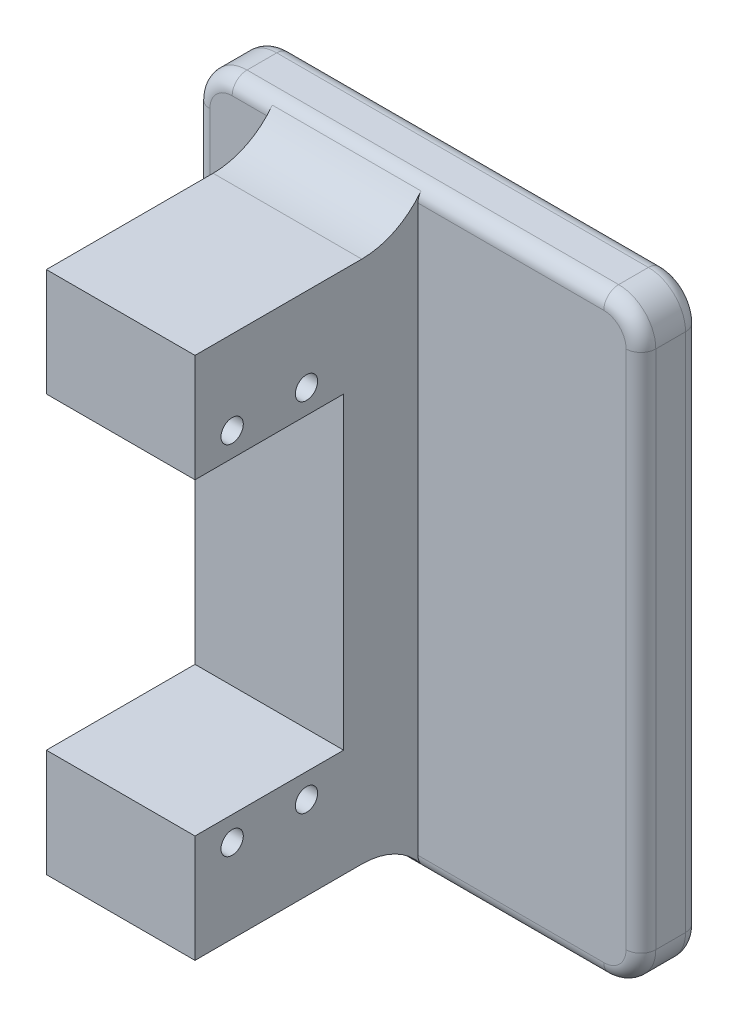
SolidWorks part; units mm, degrees
ref_plane "Front Plane" through (0, 0, 0) normal (0, 0, 1) x (1, 0, 0)
ref_plane "Top Plane" through (0, 0, 0) normal (0, 1, 0) x (1, 0, 0)
ref_plane "Right Plane" through (0, 0, 0) normal (1, 0, 0) x (0, 0, -1)
sketch "Sketch3" plane through (0, 0, 30) normal (0, 0, -1) x (-1, 0, 0)
  line L0 (95, 33.2573) -> (65, 33.2573) construction
  line L15 (80, 53.2573) -> (80, 33.2573) construction
  line L20 (55, 53.2573) -> (105, 53.2573)
  line L29 (55, -26.7427) -> (105, -26.7427)
  line L31 (110, -21.7427) -> (110, 48.2573)
  line L33 (50, -21.7427) -> (50, 48.2573)
  arc A17 (50, 48.2573) -> (55, 53.2573) centre (55, 48.2573) cw
  arc A18 (110, 48.2573) -> (105, 53.2573) centre (105, 48.2573) ccw
  arc A21 (50, -21.7427) -> (55, -26.7427) centre (55, -21.7427) ccw
  arc A22 (110, -21.7427) -> (105, -26.7427) centre (105, -21.7427) cw
  dimension "D1" = 5
extrude "Boss-Extrude1" add sketch "Sketch3" along normal blind 8
ref_plane "Plane1" through (-80, 0, 0) normal (-1, 0, 0) x (0, 0, 1)
sketch "Sketch8" plane through (0, 0, 22) normal (0, 0, -1) x (-1, 0, 0)
  line L0 (50, 13.2573) -> (110, 13.2573) construction
  line L1 (50, 48.2573) -> (50, -21.7427) construction
  line L2 (110, -21.7427) -> (110, 48.2573) construction
  line L3 (80, 13.2573) -> (80, -26.7427) construction
  line L4 (55, -26.7427) -> (105, -26.7427) construction
  line L5 (78.25, 15.3786) -> (78.25, 11.136)
  line L6 (81.75, 15.3786) -> (81.75, 11.136)
  arc A0 (78.25, 11.136) -> (81.75, 11.136) centre (80, 13.2573) ccw
  arc A1 (81.75, 15.3786) -> (78.25, 15.3786) centre (80, 13.2573) ccw
extrude "Cut-Extrude3" cut sketch "Sketch8" against normal blind 3
sketch "Sketch10" plane through (0, 0, 22) normal (0, 0, -1) x (-1, 0, 0)
  line L0 (50, 13.2573) -> (110, 13.2573) construction
  line L1 (50, 48.2573) -> (50, -21.7427) construction
  line L2 (110, -21.7427) -> (110, 48.2573) construction
  line L3 (80, 13.2573) -> (80, -26.7427) construction
  line L4 (55, -26.7427) -> (105, -26.7427) construction
  line L7 (81.75, 11.136) -> (81.75, 15.3786)
  line L8 (78.25, 15.3786) -> (78.25, 11.136)
  line L9 (81.75, 11.136) -> (81.75, 15.3786)
  line L10 (78.25, 15.3786) -> (78.25, 11.136)
  circle A3 centre (80, 13.2573) radius 9.75
  arc A5 (78.25, 11.136) -> (81.75, 11.136) centre (80, 13.2573) ccw
  arc A6 (81.75, 15.3786) -> (78.25, 15.3786) centre (80, 13.2573) ccw
  arc A7 (78.25, 11.136) -> (81.75, 11.136) centre (80, 13.2573) ccw
  arc A8 (81.75, 15.3786) -> (78.25, 15.3786) centre (80, 13.2573) ccw
  dimension "D1" = 0
extrude "Boss-Extrude4" add sketch "Sketch10" along normal blind 9
sketch "Sketch12" plane through (-80, 0, 0) normal (-1, 0, 0) x (0, 0, 1)
  line L6 (30, -21.7427) -> (30, 48.2573) construction
  line L7 (30, 48.5073) -> (60, 48.5073)
  line L8 (60, 48.5073) -> (60, 34.0073)
  line L9 (60, -21.9927) -> (30, -21.9927)
  line L11 (30, -21.9927) -> (30, 48.5073)
  line L12 (60, -7.4927) -> (60, -21.9927)
  line L13 (40, 34.0073) -> (40, -7.4927)
  line L14 (60, 34.0073) -> (40, 34.0073)
  line L15 (60, -7.4927) -> (40, -7.4927)
  point P1 (40, -6.9927)
  point P9 (40, -7.3974)
  point P13 (40, 33.5073)
  point P16 (40, 33.9062)
  dimension "D1" = 14.5
extrude "Boss-Extrude5" add sketch "Sketch12" along normal blind 20
sketch "Sketch13" plane through (-80, 0, 0) normal (1, 0, 0) x (0, 0, -1)
  circle A0 centre (-55, -10.7427) radius 1.5
  circle A1 centre (-45, -10.7427) radius 1.5
  circle A2 centre (-55, 37.2573) radius 1.5
  circle A3 centre (-45, 37.2573) radius 1.5
extrude "Cut-Extrude4" cut sketch "Sketch13" against normal blind 10
sketch "Sketch14" plane through (0, 0, 22) normal (0, 0, -1) x (-1, 0, 0)
  circle A0 centre (80, 13.2573) radius 12
extrude "Boss-Extrude6" add sketch "Sketch14" along normal blind 1
fillet "Fillet2" radius 2 16 edges at (-51.4645, 51.7928, 22) (-80, 53.2573, 22) (-108.5355, 51.7928, 22) (-110, 13.2573, 22) (-108.5355, -25.2783, 22) (-80, -26.7427, 22) (-51.4645, -25.2783, 22) (-51.4645, 51.7928, 30) (-80, 53.2573, 30) (-108.5355, 51.7928, 30) (-110, 13.2573, 30) (-108.5355, -25.2783, 30) (-80, -26.7427, 30) (-51.4645, -25.2783, 30) (-50, 13.2573, 22) (-50, 13.2573, 30)
fillet "Fillet3" radius 10 2 edges at (-90, -21.9927, 30) (-90, 48.5073, 30)
